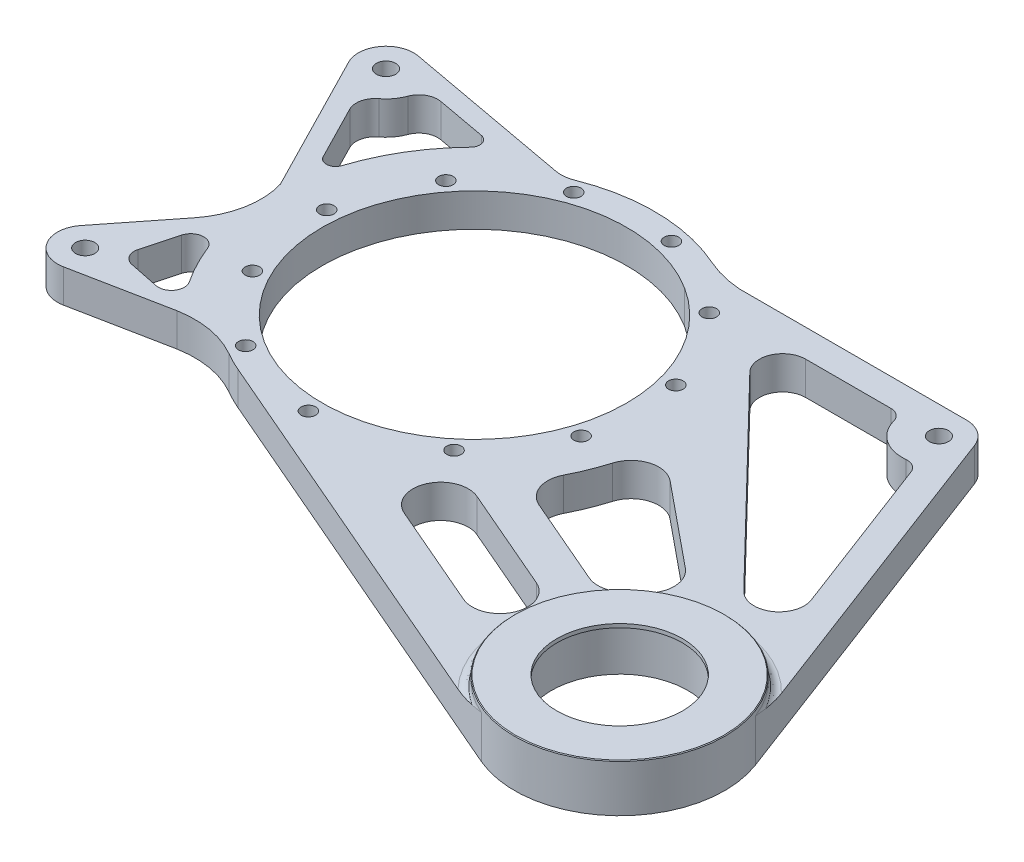
SolidWorks part; units mm, degrees
other "Markup1"
sketch "Sketch15" plane through (-673.481, -5.715, 196.22) normal (-0.8989, -0.371, 0.233) x (0.3803, -0.9249, -0.0055)
material "7075-T6 (SN)"
ref_plane "X-Y Datum" through (0, 0, 0) normal (0, 0, 1) x (1, 0, 0)
ref_plane "X-Z Datum" through (0, 0, 0) normal (0, 1, 0) x (1, 0, 0)
ref_plane "Y-Z Datum" through (0, 0, 0) normal (1, 0, 0) x (0, 0, -1)
sketch "Sketch1" plane through (0, 0, 0) normal (0, 1, 0) x (1, 0, 0)
  line L0 (-452.4939, -193.2569) -> (-599.8423, -129.6662)
  line L3 (-568.96, 0) -> (-463.042, 0) construction
  line L4 (-685.8, 0) -> (-568.96, 0) construction
  line L5 (-685.8, -143.2733) -> (-685.8, 0) construction
  line L6 (-685.8, -143.2733) -> (-575.31, -72.8215) construction
  line L7 (-575.31, -72.8215) -> (-438.15, -160.02) construction
  line L8 (-685.8, -1.6598) -> (-575.31, -72.8215) construction
  line L9 (-537.4328, -19.4168) -> (-459.3604, -19.4168)
  line L14 (-652.4813, -91.9261) -> (-669.8039, -113.9002)
  line L15 (-673.1, -130.5733) -> (-698.5, -130.5733) construction
  line L16 (-673.1, -130.5733) -> (-673.1, -155.9733) construction
  line L17 (-673.1, -155.9733) -> (-698.5, -155.9733) construction
  line L18 (-698.5, -130.5733) -> (-698.5, -155.9733) construction
  line L19 (-673.1, -130.5733) -> (-698.5, -155.9733) construction
  line L20 (-673.1, -155.9733) -> (-698.5, -130.5733) construction
  line L21 (-627.8464, -122.6884) -> (-660.4758, -129.1411)
  line L22 (-662.2354, -5.2529) -> (-604.1922, -15.9133)
  line L23 (-672.4346, -18.9616) -> (-647.7651, -67.1526)
  line L25 (-673.1, -12.7) -> (-698.5, -12.7) construction
  line L26 (-673.1, -12.7) -> (-673.1, 12.7) construction
  line L27 (-673.1, 12.7) -> (-698.5, 12.7) construction
  line L28 (-698.5, -12.7) -> (-698.5, 12.7) construction
  line L29 (-673.1, -12.7) -> (-698.5, 12.7) construction
  line L30 (-673.1, 12.7) -> (-698.5, -12.7) construction
  line L32 (-685.8, -130.5733) -> (-673.1, -130.5733) construction
  line L33 (-685.8, -129.1488) -> (-685.8, -130.5733) construction
  line L34 (-668.5282, -112.57) -> (-684.4718, -126.258) construction
  line L35 (-667.4361, -138.3507) -> (-655.5968, -126.5405) construction
  line L36 (-673.1, -139.4633) -> (-670.1269, -139.4633) construction
  line L37 (-673.1, -130.5733) -> (-673.1, -139.4633) construction
  line L38 (-685.8, -130.5733) -> (-673.1, -130.5733) construction
  line L39 (-685.8, -129.1488) -> (-685.8, -130.5733) construction
  line L40 (-668.5282, -112.57) -> (-684.4718, -126.258) construction
  line L41 (-667.4361, -138.3507) -> (-655.5968, -126.5405) construction
  line L42 (-673.1, -139.4633) -> (-670.1269, -139.4633) construction
  line L43 (-673.1, -130.5733) -> (-673.1, -139.4633) construction
  line L44 (-463.042, 0) -> (-463.042, -3.81) construction
  line L45 (-575.31, -72.8215) -> (-459.3604, -28.9418) construction
  line L46 (-450.455, -25.5624) -> (-404.305, -147.1765)
  line L47 (-575.31, -72.8215) -> (-575.31, -78.4445) construction
  line L48 (-655.8976, -11.4734) -> (-668.4375, -1.9195)
  line L49 (-670.3617, -1.27) -> (-673.1, -1.27)
  line L50 (-673.1, -1.27) -> (-673.1, -12.7)
  line L51 (-673.1, -12.7) -> (-684.53, -12.7)
  line L52 (-684.53, -12.7) -> (-684.53, -14.7065)
  line L53 (-682.9809, -17.4336) -> (-666.5478, -27.2313)
  line L56 (-673.1, -1.27) -> (-673.1, -12.7) construction
  line L57 (-673.1, -12.7) -> (-684.53, -12.7) construction
  circle A13 centre (-438.15, -160.02) radius 23.5
  circle A17 centre (-575.31, -72.8215) radius 61.9125 construction
  circle A18 centre (-575.31, -72.8215) radius 52.3875
  circle A29 centre (-438.15, -160.02) radius 36.2 construction
  arc A36 (-588.7133, -12.3772) -> (-550.1347, -16.2586) centre (-575.31, -72.8215) cw
  arc A38 (-627.8464, -122.6884) -> (-606.238, -126.4556) centre (-622.1949, -154.1272) cw
  circle A39 centre (-662.3237, -119.797) radius 3.3
  arc A45 (-684.4718, -126.258) -> (-685.8, -129.1488) centre (-681.99, -129.1488) ccw construction
  circle A46 centre (-662.3237, -119.797) radius 3.3
  circle A47 centre (-662.3237, -119.797) radius 3.3 construction
  arc A48 (-655.5968, -126.5405) -> (-668.5282, -112.57) centre (-662.3237, -119.797) ccw construction
  arc A49 (-670.1269, -139.4633) -> (-667.4361, -138.3507) centre (-670.1269, -135.6533) ccw construction
  arc A50 (-684.4718, -126.258) -> (-685.8, -129.1488) centre (-681.99, -129.1488) ccw construction
  arc A51 (-655.5968, -126.5405) -> (-668.5282, -112.57) centre (-662.3237, -119.797) ccw construction
  arc A52 (-670.1269, -139.4633) -> (-667.4361, -138.3507) centre (-670.1269, -135.6533) ccw construction
  circle A53 centre (-662.3237, -119.797) radius 9.525 construction
  arc A54 (-599.8423, -129.6662) -> (-606.238, -126.4556) centre (-575.31, -72.8215) cw
  arc A55 (-669.8039, -113.9002) -> (-660.4758, -129.1411) centre (-662.3237, -119.797) ccw
  circle A57 centre (-602.253, -5.3549) radius 10.7351 construction
  arc A58 (-588.7133, -12.3772) -> (-598.2717, -15.3244) centre (-575.31, -72.8215) ccw
  arc A59 (-668.4375, -1.9195) -> (-670.3617, -1.27) centre (-670.3617, -4.445) ccw
  arc A60 (-684.53, -14.7065) -> (-682.9809, -17.4336) centre (-681.355, -14.7065) ccw
  arc A61 (-666.5478, -27.2313) -> (-655.8976, -11.4734) centre (-661.67, -19.05) ccw
  arc A65 (-647.7651, -67.1526) -> (-652.4813, -91.9261) centre (-673.9475, -75.0039) cw
  arc A67 (-598.2717, -15.3244) -> (-604.1922, -15.9133) centre (-602.253, -5.3549) cw
  circle A68 centre (-463.042, -3.81) radius 12.7 construction
  circle A69 centre (-459.3604, -28.9418) radius 3.3
  circle A70 centre (-459.3604, -28.9418) radius 9.525 construction
  arc A71 (-550.1347, -16.2586) -> (-537.4328, -19.4168) centre (-534.8559, 18.0692) ccw
  arc A72 (-459.3604, -19.4168) -> (-450.455, -25.5624) centre (-459.3604, -28.9418) cw
  arc A73 (-452.4939, -193.2569) -> (-404.305, -147.1765) centre (-438.15, -160.02) ccw
  circle A74 centre (-685.8, -1.6598) radius 12.7 construction
  circle A75 centre (-663.956, -14.6213) radius 3.3
  circle A76 centre (-663.956, -14.6213) radius 9.525 construction
  arc A77 (-662.2354, -5.2529) -> (-672.4346, -18.9616) centre (-663.956, -14.6213) ccw
  dimension "D7" = 25.4
  dimension "D10" = 123.825
  dimension "D11" = 104.775
  dimension "D12" = 47
  dimension "D13" = 72.4
  dimension "D15" = 26.943
  dimension "D18" = 43.8797
  dimension "D24" = 31.9428
  dimension "D25" = 32.6295
  dimension "D26" = 9.344
  dimension "D29" = 21.9741
  dimension "D33" = 27.3342
  dimension "D34" = 21.844
  dimension "D23" = 19.05
  dimension "D32" = 25.4
  dimension "D38" = 3.81
  dimension "D28" = 21.4701
  dimension "D19" = 37.5744
  dimension "D17" = 25.4
  dimension "D22" = 19.05
  dimension "D1" = 685.8
  dimension "D2" = 116.84
  dimension "D3" = 222.758
  dimension "D5" = 160.02
  dimension "D6" = 117.8733
  dimension "D8" = 72.8215
  dimension "D9" = 110.49
  dimension "D14" = 25.4
  dimension "D16" = 25.1753
  dimension "D20" = 1.6598
  dimension "D21" = 25.4
  dimension "D27" = 247.65
  dimension "D30" = 7.4802
  dimension "D31" = 0
  dimension "D36" = 3.8814
  dimension "D37" = 25.4
  dimension "D43" = 0
extrude "Boss-Extrude1" add sketch "Sketch1" along normal mid plane 11.43
sketch "Sketch2" plane through (0, 5.715, 0) normal (0, 1, 0) x (1, 0, 0)
  circle A1 centre (-438.15, -160.02) radius 23.5 construction
  circle A2 centre (-438.15, -160.02) radius 36.2
  circle A3 centre (-438.15, -160.02) radius 36.2
  circle A4 centre (-438.15, -160.02) radius 23.5
  circle A5 centre (-438.15, -160.02) radius 21.595
  circle M23 centre (-438.15, -160.02) radius 23.5
  dimension "D1" = 12.7
  dimension "D2" = 1.905
extrude "Boss-Extrude2" add sketch "Sketch2" along normal blind 5.0116 contours A3 M23 | A5 M23 region at (-473.3261, 5.715, 160.02) region at (-460.9853, 5.715, 160.02)
fillet "Fillet1" radius 3.175 1 edges at (-463.1685, 5.715, 133.8567)
sketch "Sketch6" plane through (0, 5.715, 0) normal (0, -1, 0) x (1, 0, 0)
  circle A0 centre (-438.15, 160.02) radius 23.5 construction
  circle A1 centre (-438.15, 160.02) radius 21.595
  circle A2 centre (-438.15, 160.02) radius 21.595
  circle A3 centre (-438.15, 160.02) radius 23.5
  dimension "D1" = 0
extrude "Cut-Extrude1" cut sketch "Sketch6" against normal blind 3.7382
ref_point "Point1"
ref_point "Point2"
ref_plane "Plane1" through (-438.15, 1.8691, 160.02) normal (0.8439, 0, 0.5365) x (0.5365, 0, -0.8439)
ref_plane "Plane2" through (-376.7454, 0, -239.5133) normal (0.8439, 0, 0.5365) x (0.5365, 0, -0.8439)
split line "Split Line1"
split line "Split Line2"
sketch "Sketch8" plane through (0, -5.715, 0) normal (0, -1, 0) x (1, 0, 0)
  circle A0 centre (-575.31, 72.8215) radius 61.9125 construction
  circle A1 centre (-575.31, 72.8215) radius 61.9125
split line "Split Line5"
sketch "Sketch11" plane through (0, -5.715, 0) normal (0, -1, 0) x (1, 0, 0)
  line L0 (-432.5065, 99.7069) -> (-453.4854, 44.4233)
  line L1 (-505.1999, 28.9418) -> (-475.9191, 28.9418)
  line L2 (-446.7272, 108.7426) -> (-510.9245, 42.4551)
  line L6 (-459.3604, 19.4168) -> (-537.4328, 19.4168) construction
  line L8 (-520.863, 126.4041) -> (-484.9545, 141.901)
  line L9 (-507.6372, 118.2797) -> (-477.2649, 131.3874)
  line L10 (-492.3337, 88.4924) -> (-463.6054, 111.9621)
  line L19 (-658.1742, 32.8834) -> (-648.5837, 51.6181)
  line L20 (-644.8026, 14.9109) -> (-627.7247, 18.0475)
  line L21 (-672.4346, 18.9616) -> (-647.7651, 67.1526) construction
  line L22 (-662.2354, 5.2529) -> (-604.1922, 15.9133) construction
  line L23 (-672.4346, 18.9616) -> (-647.7651, 67.1526) construction
  line L24 (-662.2354, 5.2529) -> (-604.1922, 15.9133) construction
  line L25 (-662.3237, 119.797) -> (-575.31, 72.8215) construction
  line L26 (-652.7583, 111.1604) -> (-649.5762, 99.3396)
  line L27 (-649.3552, 116.671) -> (-638.88, 118.8094)
  line L28 (-528.4114, 143.8948) -> (-492.5029, 159.3917)
  line L29 (-599.8423, 129.6662) -> (-452.4939, 193.2569) construction
  line L30 (-404.305, 147.1765) -> (-450.455, 25.5624) construction
  circle A0 centre (-440.5484, 102.7586) radius 8.6015 construction
  circle A1 centre (-505.1999, 36.911) radius 7.9692 construction
  circle A2 centre (-475.9191, 33.3868) radius 4.445 construction
  circle A3 centre (-457.6413, 46.0004) radius 4.445 construction
  arc A4 (-475.9191, 28.9418) -> (-471.6261, 32.2344) centre (-475.9191, 33.3868) ccw
  circle A6 centre (-575.31, 72.8215) radius 70.8025
  circle A7 centre (-575.31, 72.8215) radius 70.8025 construction
  circle A9 centre (-459.3604, 28.9418) radius 12.7 construction
  arc A10 (-471.6261, 32.2344) -> (-458.087, 41.5778) centre (-459.3604, 28.9418) cw
  arc A11 (-453.4854, 44.4233) -> (-458.087, 41.5778) centre (-457.6413, 46.0004) cw
  arc A12 (-432.5065, 99.7069) -> (-446.7272, 108.7426) centre (-440.5484, 102.7586) ccw
  arc A13 (-505.1999, 28.9418) -> (-510.9245, 42.4551) centre (-505.1999, 36.911) cw
  circle A14 centre (-524.6372, 135.1494) radius 9.525 construction
  circle A15 centre (-488.7287, 150.6463) radius 9.525 construction
  circle A16 centre (-503.863, 109.5343) radius 9.525 construction
  circle A17 centre (-473.4907, 122.642) radius 9.525 construction
  arc A19 (-512.335, 105.181) -> (-507.4844, 93.1359) centre (-575.31, 72.8215) cw
  circle A20 centre (-498.3598, 95.8688) radius 9.525 construction
  arc A23 (-528.4114, 143.8948) -> (-520.863, 126.4041) centre (-524.6372, 135.1494) ccw
  arc A24 (-492.5029, 159.3917) -> (-484.9545, 141.901) centre (-488.7287, 150.6463) cw
  arc A25 (-507.6372, 118.2797) -> (-512.335, 105.181) centre (-503.863, 109.5343) ccw
  arc A26 (-507.4844, 93.1359) -> (-492.3337, 88.4924) centre (-498.3598, 95.8688) ccw
  circle A28 centre (-469.6315, 119.3385) radius 9.525 construction
  arc A29 (-466.9467, 129.5632) -> (-463.8022, 126.8714) centre (-438.15, 160.02) ccw
  arc A30 (-477.2649, 131.3874) -> (-466.9467, 129.5632) centre (-473.4907, 122.642) cw
  arc A31 (-463.8022, 126.8714) -> (-463.6054, 111.9621) centre (-469.6315, 119.3385) cw
  arc A34 (-468.5591, 188.8671) -> (-407.9721, 130.9312) centre (-438.15, 160.02) ccw
  arc A35 (-468.5591, 188.8671) -> (-407.9721, 130.9312) centre (-438.15, 160.02) ccw construction
  circle A52 centre (-652.4088, 29.932) radius 6.477 construction
  circle A53 centre (-645.9727, 21.2814) radius 6.477 construction
  circle A54 centre (-645.7462, 50.1656) radius 3.1877 construction
  circle A55 centre (-628.3005, 21.1828) radius 3.1877 construction
  arc A57 (-642.7116, 51.1417) -> (-626.0175, 23.4075) centre (-575.31, 72.8215) ccw
  arc A60 (-642.7116, 51.1417) -> (-648.5837, 51.6181) centre (-645.7462, 50.1656) ccw
  arc A61 (-626.0175, 23.4075) -> (-627.7247, 18.0475) centre (-628.3005, 21.1828) cw
  circle A63 centre (-648.4662, 112.3158) radius 4.445 construction
  circle A64 centre (-637.9909, 114.4542) radius 4.445 construction
  circle A65 centre (-645.284, 100.4951) radius 4.445 construction
  arc A66 (-641.1505, 98.8604) -> (-634.2883, 111.9949) centre (-575.31, 72.8215) cw
  arc A67 (-652.7583, 111.1604) -> (-649.3552, 116.671) centre (-648.4662, 112.3158) cw
  arc A68 (-638.88, 118.8094) -> (-634.2883, 111.9949) centre (-637.9909, 114.4542) cw
  arc A69 (-641.1505, 98.8604) -> (-649.5762, 99.3396) centre (-645.284, 100.4951) cw
  circle A70 centre (-459.3604, 28.9418) radius 3.3 construction
  circle A71 centre (-459.3604, 28.9418) radius 3.3 construction
  arc A74 (-656.3088, 24.7608) -> (-652.0465, 19.0319) centre (-663.956, 14.6213) cw
  circle A75 centre (-663.956, 14.6213) radius 12.7
  circle A76 centre (-663.956, 14.6213) radius 12.7 construction
  arc A77 (-658.1742, 32.8834) -> (-656.3088, 24.7608) centre (-652.4088, 29.932) ccw
  arc A78 (-652.0465, 19.0319) -> (-644.8026, 14.9109) centre (-645.9727, 21.2814) ccw
  dimension "D3" = 8.89
  dimension "D6" = 25.4
  dimension "D10" = 19.05
  dimension "D15" = 12.954
  dimension "D16" = 6.3754
  dimension "D19" = 8.89
  dimension "D4" = 9.525
  dimension "D5" = 9.525
  dimension "D7" = 73.8169
  dimension "D8" = 29.0831
  dimension "D9" = 15.24
  dimension "D11" = 12.7
  dimension "D12" = 14.732
  dimension "D14" = 5.08
  dimension "D17" = 6.35
  dimension "D18" = 6.35
  dimension "D20" = 8.89
  dimension "D21" = 6.858
  dimension "D22" = 15.748
  dimension "D23" = 45.8396
  dimension "D1" = 8.89
  dimension "D13" = 2.54
  dimension "D24" = 3.175
extrude "Cut-Extrude3" cut sketch "Sketch11" against normal through all
sketch "Sketch12" plane through (0, -5.715, 0) normal (0, -1, 0) x (1, 0, 0)
  line L0 (-575.31, 72.8215) -> (-575.31, 159.4351) construction
  line L1 (-685.8, 143.2733) -> (-685.8, 0) construction
  line L2 (-685.8, 143.2733) -> (-685.8, 0)
  arc A0 (-603.416, 117.0312) -> (-547.204, 28.6117) centre (-575.31, 72.8215) ccw construction
  arc A1 (-547.204, 28.6117) -> (-603.416, 117.0312) centre (-575.31, 72.8215) ccw construction
  arc A2 (-603.416, 117.0312) -> (-547.204, 28.6117) centre (-575.31, 72.8215) ccw construction
  arc A3 (-547.204, 28.6117) -> (-603.416, 117.0312) centre (-575.31, 72.8215) ccw construction
  circle A4 centre (-575.31, 129.9715) radius 4.7625 construction
  arc A6 (-550.1347, 16.2586) -> (-599.8423, 129.6662) centre (-575.31, 72.8215) ccw construction
hole_wizard "Ø5.0mm Dowel Hole1" positions "Sketch13" profile "Sketch14" hole size "Ø5.0" standard "ANSI Metric" end condition through all
sketch "Sketch13" plane through (0, -5.715, 0) normal (0, -1, 0) x (-1, 0, 0)
  point P0 (575.31, -129.9715)
sketch "Sketch14" plane through (-575.31, -5.715, 129.9715) normal (1, 0, 0) x (0, 0, -1)
  line L0 (0, 0) -> (0, 16.4416)
  line L1 (0, 16.4416) -> (2.5, 16.4416)
  line L2 (2.5, 16.4416) -> (2.5, 0.025)
  line L3 (2.5, 0.025) -> (2.525, 0)
  line L5 (2.525, 0) -> (0, 0)
  line L6 (-2.5, 0.025) -> (-2.525, 0) construction
  line L11 (0, -6.35) -> (0, 107.95) construction
  dimension "Thru Hole Dia." = 5
  dimension "Thru Hole Depth" = 16.4416
  dimension "Near C'Sink Dia." = 5.05
  dimension "Near C'Sink Angle" = 90
pattern_circular "CirPattern1" count 11 every 32 about axis through (-575.31, 5.715, 72.8215) along (0, -1, 0) of "Ø5.0mm Dowel Hole1"
chamfer "Chamfer1" distance 0.254 angle 45 1 edges at (-438.15, 10.7266, 196.22)
